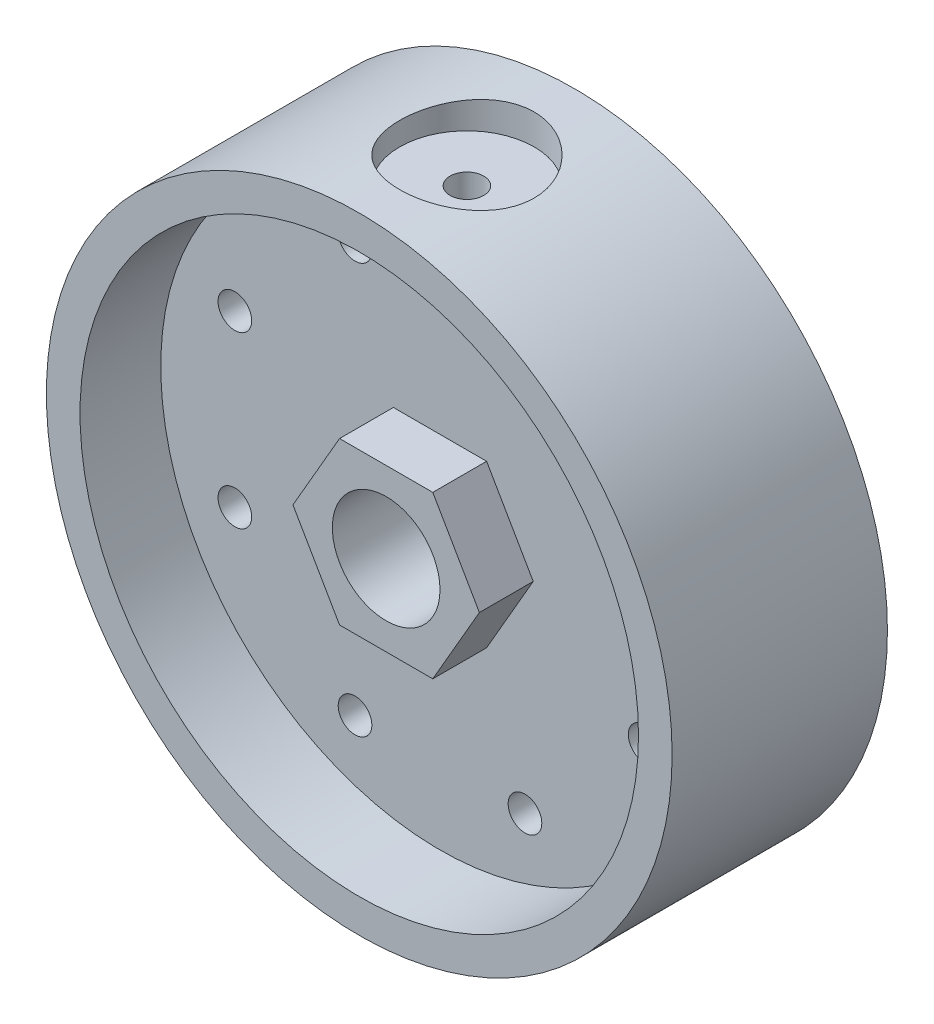
SolidWorks part; units mm, degrees
ref_plane "Plan de face" through (0, 0, 0) normal (0, 0, 1) x (1, 0, 0)
ref_plane "Plan de dessus" through (0, 0, 0) normal (0, 1, 0) x (1, 0, 0)
ref_plane "Plan de droite" through (0, 0, 0) normal (1, 0, 0) x (0, 0, -1)
ref_axis "Axis1" through (0, 0, -6.6) along (0, 0, 1)
sketch "Esquisse1" plane through (0, 0, 0) normal (0, 0, 1) x (1, 0, 0)
  circle A0 centre (0, 0) radius 23.25
  circle A1 centre (0, 0) radius 20.75
  dimension "D1" = 46.5
  dimension "D2" = 2.5
  dimension "D3" = 41.5
extrude "Main" add sketch "Esquisse1" along normal mid plane 16
sketch "Esquisse2" plane through (0, 0, 0) normal (0, 0, 1) x (1, 0, 0)
  circle A0 centre (0, 0) radius 20.75
  circle A1 centre (0, 0) radius 20.75 construction
extrude "CentralPart" add sketch "Esquisse2" along normal mid plane 4
sketch "Esquisse3" plane through (0, 0, 0) normal (0, 0, 1) x (1, 0, 0)
  line L1 (-3.4641, 6) -> (-6.9282, 0)
  line L2 (-6.9282, 0) -> (-3.4641, -6)
  line L3 (-3.4641, -6) -> (3.4641, -6)
  line L4 (3.4641, -6) -> (6.9282, 0)
  line L5 (6.9282, 0) -> (3.4641, 6)
  line L6 (3.4641, 6) -> (-3.4641, 6)
  line L7 (6.6, 0) -> (-6.6, 0) construction
  circle A0 centre (0, 0) radius 6 construction
  dimension "D1" = 12
extrude "Hexagonal" add sketch "Esquisse3" along normal blind 6
sketch "Esquisse5" plane through (0, 0, 0) normal (0, 0, 1) x (1, 0, 0)
  circle A0 centre (0, 0) radius 4
  dimension "D1" = 8
extrude "CentralHole" cut sketch "Esquisse5" against normal mid plane 12
ref_plane "Plane1" through (0, 21, 0) normal (0, 1, 0) x (1, 0, 0)
sketch "Sketch1" plane through (0, 21, 0) normal (0, 1, 0) x (1, 0, 0)
  circle A0 centre (0, 0) radius 1.25
  point P3 (0, 0)
  dimension "D1" = 2.5
extrude "FixTopHole" cut sketch "Sketch1" against normal blind 22 and the other way through all
sketch "Sketch2" plane through (0, 21, 0) normal (0, 1, 0) x (1, 0, 0)
  circle A0 centre (0, 0) radius 5
  point P2 (0, 0)
  dimension "D1" = 10
extrude "Cut-Extrude2" cut sketch "Sketch2" along normal through all
sketch "Sketch3" plane through (0, 0, 0) normal (0, 0, 1) x (1, 0, 0)
  line L1 (-6.3143, 15.244) -> (0, 0) construction
  line L2 (0, 17.3403) -> (0, 0) construction
  line L3 (0, -6.6) -> (0, 6.6) construction
  circle A0 centre (-6.3143, 15.244) radius 1.25
  dimension "D3" = 2.5
  dimension "D1" = 16.5
  dimension "D2" = 22.5
extrude "HubFixHole" cut sketch "Sketch3" against normal through all both and the other way through all
pattern_circular "CirPattern1" count 8 every 45 about axis through (0, 0, -6.6) along (0, 0, 1) of "HubFixHole"
